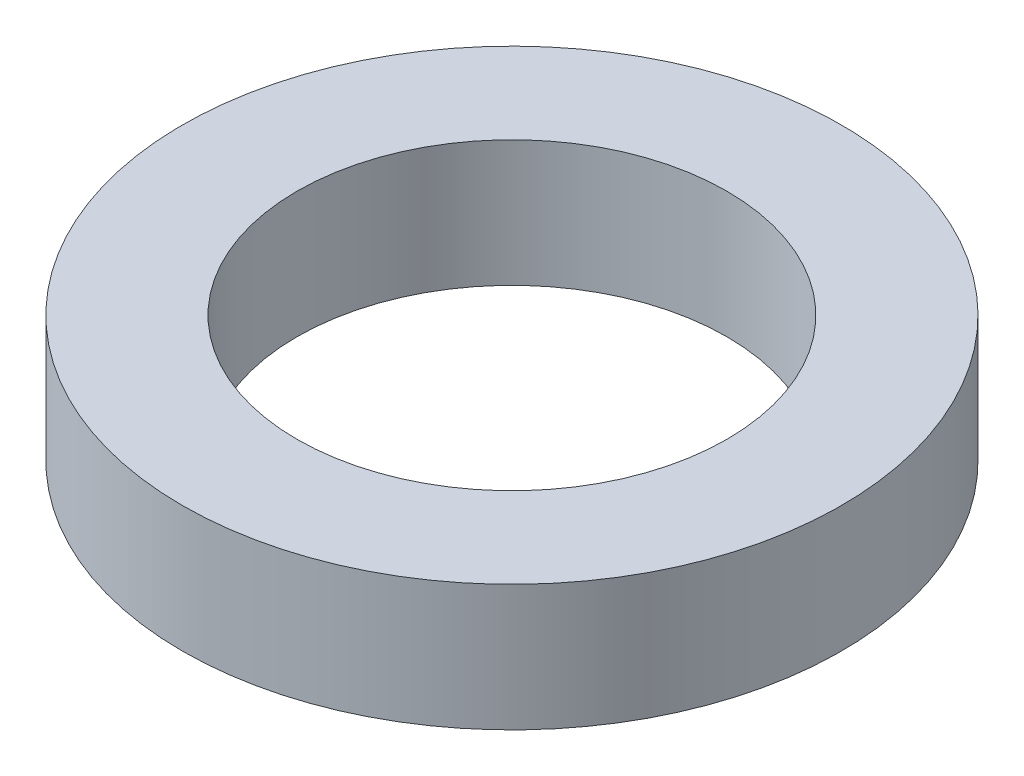
SolidWorks part; units mm, degrees
ref_plane "Front Plane" through (0, 0, 0) normal (0, 0, 1) x (1, 0, 0)
ref_plane "Top Plane" through (0, 0, 0) normal (0, 1, 0) x (1, 0, 0)
ref_plane "Right Plane" through (0, 0, 0) normal (1, 0, 0) x (0, 0, -1)
sketch "Sketch1" plane through (0, 0, 0) normal (0, 1, 0) x (1, 0, 0)
  circle A0 centre (0, 0) radius 57.5
  dimension "FLANGE_OD" = 115
extrude "Boss-Extrude1" add sketch "Sketch1" along normal blind 22
sketch "Sketch2" plane through (0, 0, 0) normal (0, 1, 0) x (1, 0, 0)
  circle A0 centre (0, 0) radius 37.5
  dimension "BORE_D" = 75
extrude "Cut-Extrude1" cut sketch "Sketch2" along normal through all
sketch "Sketch3" plane through (0, 22, 0) normal (0, 1, 0) x (1, 0, 0)
  circle A0 centre (0, 0) radius 22.938 construction
  circle A1 centre (-22.938, 0) radius 3.1648
  dimension "BOLT_D" = 6.3296
  dimension "BOLT_PCD" = 45.8761
extrude "Cut-Extrude2" cut sketch "Sketch3" against normal blind 18.177 rebuild error yes
pattern_circular "CirPattern1" count 6 over 360 rebuild error yes
